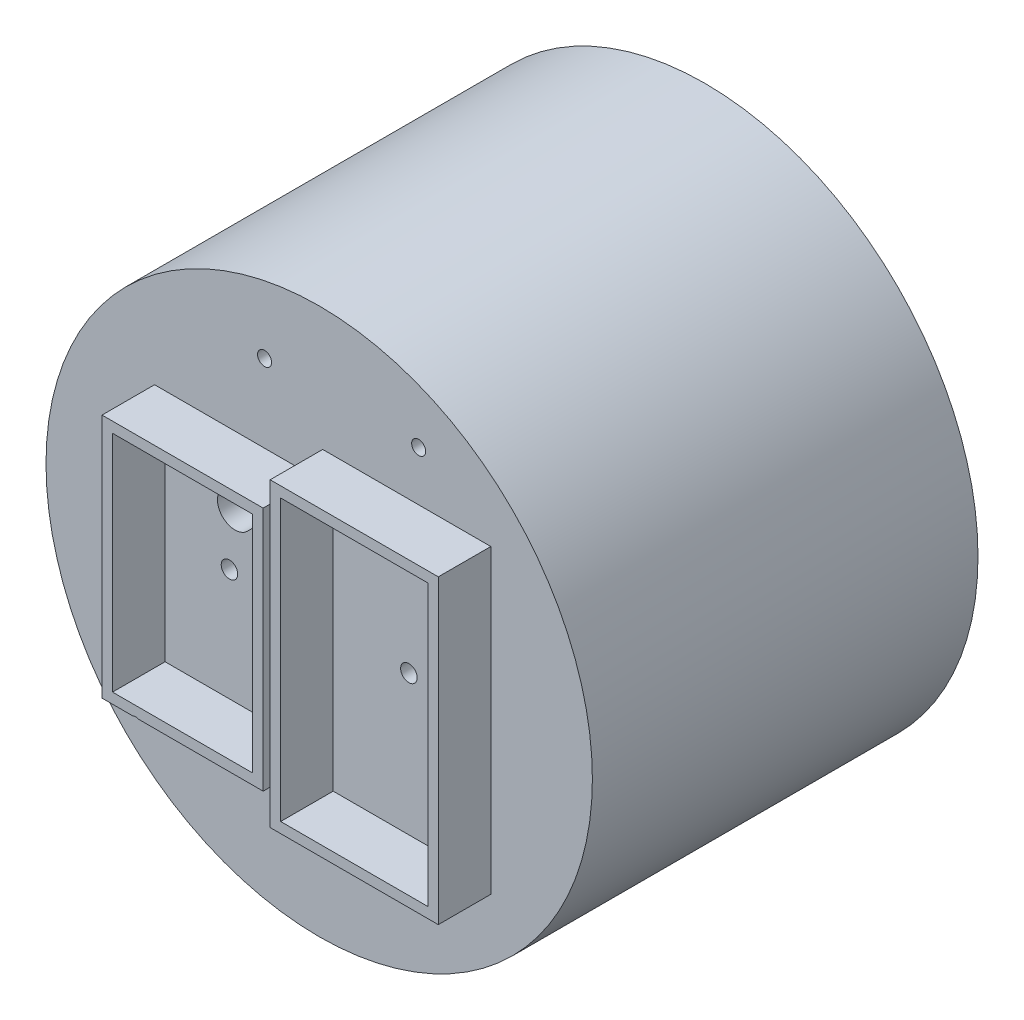
SolidWorks part; units mm, degrees
ref_plane "Front Plane" through (0, 0, 0) normal (0, 0, 1) x (1, 0, 0)
ref_plane "Top Plane" through (0, 0, 0) normal (0, 1, 0) x (1, 0, 0)
ref_plane "Right Plane" through (0, 0, 0) normal (1, 0, 0) x (0, 0, -1)
sketch "Sketch2" plane through (0, 0, 0) normal (1, 0, 0) x (0, 0, -1)
  line L0 (0, 12.5857) -> (0, 0)
  line L1 (0, -12.5857) -> (4.4704, -13.9065)
  line L2 (4.4704, 13.9065) -> (4.4704, 16.4465)
  line L3 (4.4704, 16.4465) -> (0, 16.4465)
  line L4 (0, 16.4465) -> (0, 44.45)
  line L5 (0, 44.45) -> (59.7512, 44.45)
  line L6 (59.7512, 44.45) -> (59.7512, 39.37)
  line L7 (59.7512, 39.37) -> (64.8312, 39.37)
  line L8 (64.8312, 39.37) -> (64.8312, 49.53)
  line L9 (64.8312, 49.53) -> (-5.08, 49.53)
  line L10 (-5.08, 49.53) -> (-5.08, 0)
  line L12 (0, 0) -> (-5.08, 0)
  line L17 (0, 12.0425) -> (0, 12.5857) construction
  line L19 (4.4704, 13.9065) -> (0, 12.5857)
  line L20 (4.4704, 13.9065) -> (0, 12.5857)
  line L21 (0, -12.5857) -> (4.4704, -13.9065)
  dimension "D1" = 2.54
  dimension "D2" = 5.08
  dimension "D3" = 44.45
  dimension "D4" = 5.08
  dimension "D5" = 5.08
  dimension "D6" = 5.08
revolve "Revolve1" add sketch "Sketch2" angle 360 about L12 region at (0, 6.2928, 0.8568)
sketch "Sketch4" plane through (0, 0, 0) normal (0, 0, 1) x (1, 0, 0)
  line L0 (-3.6576, 12.0425) -> (-3.6576, 10.4835)
  line L1 (-3.6576, 16.265) -> (-3.6576, 12.0425)
  line L2 (-3.6576, 16.265) -> (-3.6576, 12.0425) construction
  line L3 (-3.6576, 12.0425) -> (-3.6576, 10.4835) construction
  line L4 (3.6576, 12.0425) -> (3.6576, 10.4835)
  line L5 (3.6576, 16.265) -> (3.6576, 12.0425)
  line L6 (3.6576, 16.265) -> (3.6576, 12.0425) construction
  line L7 (3.6576, 12.0425) -> (3.6576, 10.4835) construction
  line L8 (12.0425, 3.6576) -> (10.4835, 3.6576)
  line L9 (16.265, 3.6576) -> (12.0425, 3.6576)
  line L10 (16.265, 3.6576) -> (12.0425, 3.6576) construction
  line L11 (12.0425, 3.6576) -> (10.4835, 3.6576) construction
  line L12 (12.0425, -3.6576) -> (10.4835, -3.6576)
  line L13 (16.265, -3.6576) -> (12.0425, -3.6576)
  line L14 (16.265, -3.6576) -> (12.0425, -3.6576) construction
  line L15 (12.0425, -3.6576) -> (10.4835, -3.6576) construction
  line L16 (3.6576, -12.0425) -> (3.6576, -10.4835)
  line L17 (3.6576, -16.265) -> (3.6576, -12.0425)
  line L18 (3.6576, -16.265) -> (3.6576, -12.0425) construction
  line L19 (3.6576, -12.0425) -> (3.6576, -10.4835) construction
  line L20 (-3.6576, -12.0425) -> (-3.6576, -10.4835)
  line L21 (-3.6576, -16.265) -> (-3.6576, -12.0425)
  line L22 (-3.6576, -16.265) -> (-3.6576, -12.0425) construction
  line L23 (-3.6576, -12.0425) -> (-3.6576, -10.4835) construction
  line L24 (-12.0425, 3.6576) -> (-10.4835, 3.6576)
  line L25 (-16.265, 3.6576) -> (-12.0425, 3.6576)
  line L26 (-16.265, 3.6576) -> (-12.0425, 3.6576) construction
  line L27 (-12.0425, 3.6576) -> (-10.4835, 3.6576) construction
  line L28 (-4.1656, -12.0425) -> (-4.1656, -10.4835)
  line L29 (-4.1656, -16.265) -> (-4.1656, -12.0425)
  line L30 (4.1656, -16.265) -> (4.1656, -12.0425)
  line L31 (4.1656, -12.0425) -> (4.1656, -10.4835)
  line L32 (12.0425, -4.1656) -> (10.4835, -4.1656)
  line L33 (16.265, -4.1656) -> (12.0425, -4.1656)
  line L34 (16.265, 4.1656) -> (12.0425, 4.1656)
  line L35 (12.0425, 4.1656) -> (10.4835, 4.1656)
  line L36 (4.1656, 12.0425) -> (4.1656, 10.4835)
  line L37 (4.1656, 16.265) -> (4.1656, 12.0425)
  line L38 (-4.1656, 16.265) -> (-4.1656, 12.0425)
  line L39 (-4.1656, 12.0425) -> (-4.1656, 10.4835)
  line L40 (-12.0425, 4.1656) -> (-10.4835, 4.1656)
  line L41 (-16.265, 4.1656) -> (-12.0425, 4.1656)
  line L42 (-10.4835, -4.1656) -> (-16.265, -4.1656)
  line L43 (-9.8783, 15.2664) -> (-15.2664, 9.8783) construction
  line L44 (-7.6332, 13.0214) -> (-13.0214, 7.6332)
  line L45 (-12.1233, 17.5115) -> (-17.5115, 12.1233)
  line L46 (0, 0) -> (-26.7135, 26.7135) construction
  line L47 (0, 0) -> (0, 36.3192) construction
  arc A0 (-10.4835, 3.6576) -> (-3.6576, 10.4835) centre (-10.4835, 10.4835) ccw
  arc A1 (-10.4835, 3.6576) -> (-3.6576, 10.4835) centre (-10.4835, 10.4835) ccw construction
  arc A2 (3.6576, 16.265) -> (-3.6576, 16.265) centre (0, 16.265) ccw
  arc A3 (3.6576, 16.265) -> (-3.6576, 16.265) centre (0, 16.265) ccw construction
  arc A4 (3.6576, 10.4835) -> (10.4835, 3.6576) centre (10.4835, 10.4835) ccw
  arc A5 (3.6576, 10.4835) -> (10.4835, 3.6576) centre (10.4835, 10.4835) ccw construction
  arc A6 (16.265, -3.6576) -> (16.265, 3.6576) centre (16.265, 0) ccw
  arc A7 (16.265, -3.6576) -> (16.265, 3.6576) centre (16.265, 0) ccw construction
  arc A8 (10.4835, -3.6576) -> (3.6576, -10.4835) centre (10.4835, -10.4835) ccw
  arc A9 (10.4835, -3.6576) -> (3.6576, -10.4835) centre (10.4835, -10.4835) ccw construction
  arc A10 (-3.6576, -16.265) -> (3.6576, -16.265) centre (0, -16.265) ccw
  arc A11 (-3.6576, -16.265) -> (3.6576, -16.265) centre (0, -16.265) ccw construction
  arc A12 (-3.6576, -10.4835) -> (-10.4835, -3.6576) centre (-10.4835, -10.4835) ccw
  arc A13 (-3.6576, -10.4835) -> (-10.4835, -3.6576) centre (-10.4835, -10.4835) ccw construction
  arc A14 (-16.265, 3.6576) -> (-16.265, -3.6576) centre (-16.265, 0) ccw
  arc A15 (-16.265, 3.6576) -> (-16.265, -3.6576) centre (-16.265, 0) ccw construction
  arc A16 (-4.1656, -10.4835) -> (-10.4835, -4.1656) centre (-10.4835, -10.4835) ccw
  arc A17 (-4.1656, -16.265) -> (4.1656, -16.265) centre (0, -16.265) ccw
  arc A18 (10.4835, -4.1656) -> (4.1656, -10.4835) centre (10.4835, -10.4835) ccw
  arc A19 (16.265, -4.1656) -> (16.265, 4.1656) centre (16.265, 0) ccw
  arc A20 (4.1656, 10.4835) -> (10.4835, 4.1656) centre (10.4835, 10.4835) ccw
  arc A21 (4.1656, 16.265) -> (-4.1656, 16.265) centre (0, 16.265) ccw
  arc A22 (-10.4835, 4.1656) -> (-4.1656, 10.4835) centre (-10.4835, 10.4835) ccw
  arc A23 (-16.265, 4.1656) -> (-16.265, -4.1656) centre (-16.265, 0) ccw
  circle A24 centre (16.265, 0) radius 1.5
  circle A25 centre (0, 16.265) radius 1.5
  circle A26 centre (-16.265, 0) radius 1.5
  circle A27 centre (0, -16.265) radius 1.5
  arc A28 (-7.6332, 13.0214) -> (-12.1233, 17.5115) centre (-9.8783, 15.2664) ccw
  arc A29 (-17.5115, 12.1233) -> (-13.0214, 7.6332) centre (-15.2664, 9.8783) ccw
  point P68 (-12.5724, 12.5724)
  dimension "D2" = 3
  dimension "D3" = 45
  dimension "D4" = 17.78
  dimension "D5" = 6.35
  dimension "D6" = 7.62
  dimension "D1" = 0.508
extrude "Cut-Extrude2" cut sketch "Sketch4" against normal blind 12.7 contours A17 L30 L31 A18 L32 L33 A19 L34 L35 A20 L36 L37 A21 L38 L39 A22 L40 L41 A23 L42 A16 L28 L29
extrude "Cut-Extrude3" cut sketch "Sketch4<3>" along normal blind 9.525 contours A27 | A26 | A24 | A25 | A28 L45 A29 L44 region at (16.265, 0, 0) region at (0, 16.265, 0) region at (-16.265, 0, 0) region at (0, -16.265, 0)
sketch "Sketch4<3>" plane through (0, 0, 0) normal (0, 0, 1) x (1, 0, 0) same geometry as "Sketch4"
sketch "Sketch6" plane through (0, 0, 5.08) normal (0, 0, 1) x (1, 0, 0)
  line L0 (-29.845, 22.225) -> (-0.635, 22.225)
  line L1 (2.54, 25.4) -> (29.21, 25.4)
  line L2 (2.54, 25.4) -> (2.54, -25.4)
  line L3 (2.54, -25.4) -> (29.21, -25.4)
  line L4 (29.21, 25.4) -> (29.21, -25.4)
  line L5 (2.54, 25.4) -> (29.21, -25.4) construction
  line L6 (2.54, -25.4) -> (29.21, 25.4) construction
  line L7 (-27.94, 20.32) -> (-2.54, 20.32)
  line L8 (-27.94, 20.32) -> (-27.94, -20.32)
  line L9 (-27.94, -20.32) -> (-2.54, -20.32)
  line L10 (-2.54, 20.32) -> (-2.54, -20.32)
  line L11 (-27.94, 20.32) -> (-2.54, -20.32) construction
  line L12 (-27.94, -20.32) -> (-2.54, 20.32) construction
  line L13 (-0.635, 22.225) -> (-0.635, -22.225)
  line L14 (-29.845, -22.225) -> (-0.635, -22.225)
  line L15 (-29.845, 22.225) -> (-29.845, -22.225)
  line L16 (0.635, 27.305) -> (0.635, -27.305)
  line L17 (0.635, -27.305) -> (31.115, -27.305)
  line L18 (31.115, 27.305) -> (31.115, -27.305)
  line L19 (0.635, 27.305) -> (31.115, 27.305)
  circle A0 centre (-9.906, 36.322) radius 1.27
  circle A1 centre (-23.749, -23.368) radius 1.27
  circle A2 centre (23.114, -15.748) radius 1.27
  circle A3 centre (18.034, 36.322) radius 1.27
  circle A4 centre (18.034, 36.322) radius 1.5875 construction
  circle A5 centre (-9.906, 36.322) radius 1.5875 construction
  circle A6 centre (-23.749, -23.368) radius 1.5 construction
  circle A7 centre (23.114, -15.748) radius 1.5875 construction
  point P4 (15.875, 0)
  point P9 (-15.24, 0)
  circle M34 centre (0, 16.265) radius 1.5
  circle M37 centre (0, -16.265) radius 1.5
  dimension "D9" = 2.54
  dimension "D1" = 26.67
  dimension "D2" = 50.8
  dimension "D3" = 2.54
  dimension "D4" = 25.4
  dimension "D5" = 40.64
  dimension "D6" = 25.4
  dimension "D7" = 2.54
  dimension "D8" = 20.32
  dimension "D10" = 1.905
extrude "Boss-Extrude2" add sketch "Sketch6" along normal blind 9.525 contours L0 L15 L14 L13 L7 L10 L9 L8 | L19 L16 L17 L18 L1 L4 L3 L2 | L13 M34 | L16 M34 | L16 M37 | L13 M37 region at (-15.24, 21.6931, 5.08) region at (-0.9913, 16.265, 5.08) region at (0.9913, 16.265, 5.08) region at (1.2604, 22.4645, 5.08) region at (-0.9913, -16.265, 5.08) region at (0.9913, -16.265, 5.08)
extrude "Cut-Extrude4" cut sketch "Sketch6<3>" against normal blind 9.525 contours A1 | A2 | A0 | A3 region at (-23.749, -23.3907, 5.08) region at (-9.906, 36.322, 5.08) region at (23.114, -15.748, 5.08) region at (18.034, 36.322, 5.08)
sketch "Sketch6<3>" plane through (0, 0, 5.08) normal (0, 0, 1) x (1, 0, 0) same geometry as "Sketch6"
